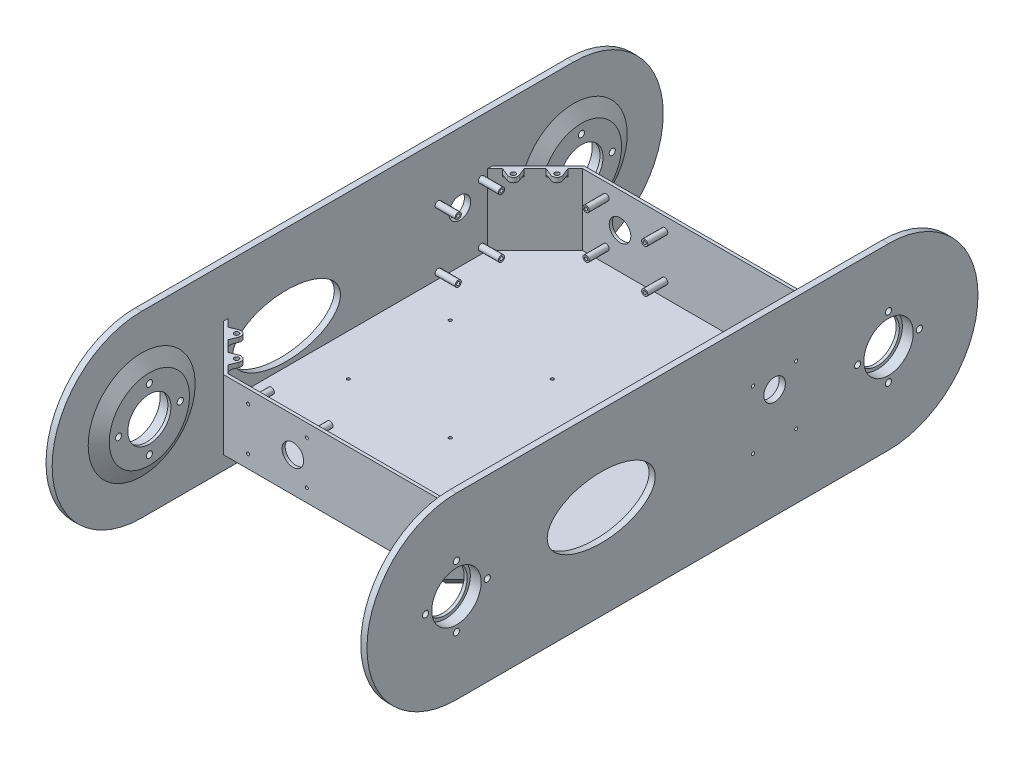
SolidWorks part; units mm, degrees
material "Zoltek Panex 33"
ref_plane "Front Plane" through (0, 0, 0) normal (0, 0, 1) x (1, 0, 0)
ref_plane "Top Plane" through (0, 0, 0) normal (0, 1, 0) x (1, 0, 0)
ref_plane "Right Plane" through (0, 0, 0) normal (1, 0, 0) x (0, 0, -1)
sketch "Sketch1" plane through (0, 0, 0) normal (0, 1, 0) x (1, 0, 0)
  line L1 (-100, -117) -> (100, -117)
  line L2 (-100, -117) -> (-100, 117)
  line L3 (-100, 117) -> (100, 117)
  line L4 (100, -117) -> (100, 117)
  line L5 (-100, -117) -> (100, 117) construction
  line L6 (-100, 117) -> (100, -117) construction
  point P0 (0, 0)
  dimension "D1" = 200
  dimension "D2" = 234
extrude "Boss-Extrude1" add sketch "Sketch1" along normal blind 52 contours L3 L4 L1 L2
chamfer "Chamfer1" distance 30 angle 45 4 edges at (-100, 26, -117) (100, 26, -117) (-100, 26, 117) (100, 26, 117)
sketch "Sketch2" plane through (100, 0, 0) normal (1, 0, 0) x (0, 0, -1)
  line L0 (117, 26) -> (-117, 26) construction
  line L1 (117, 52) -> (117, 0) construction
  line L2 (-117, 52) -> (-117, 0) construction
  line L3 (-140, 26) -> (140, 26) construction
  line L4 (-140, 84) -> (140, 84)
  line L5 (-140, -32) -> (140, -32)
  arc A0 (-140, 84) -> (-140, -32) centre (-140, 26) ccw
  arc A1 (140, -32) -> (140, 84) centre (140, 26) ccw
  point P8 (0, 26)
  dimension "D2" = 58
  dimension "D1" = 280
extrude "Boss-Extrude2" add sketch "Sketch2" along normal blind 4
ref_plane "Plane1" through (95, 0, 0) normal (-1, 0, 0) x (0, 0, 1)
sketch "Sketch3" plane through (95, 0, 0) normal (-1, 0, 0) x (0, 0, 1)
  circle A0 centre (140, 26) radius 16
  circle A1 centre (140, 26) radius 26
  dimension "D1" = 32
  dimension "D2" = 52
extrude "Boss-Extrude3" add sketch "Sketch3" against normal up to surface (5 mm away) draft 60 contours A1 up to face at (100, 26, 0) draft outward yes
sketch "Sketch4" plane through (95, 0, 0) normal (-1, 0, 0) x (0, 0, 1)
  circle A0 centre (140, 26) radius 14
  dimension "D1" = 28
extrude "Cut-Extrude1" cut sketch "Sketch4" against normal blind 2
sketch "Sketch5" plane through (97, 0, 0) normal (-1, 0, 0) x (0, 0, 1)
  circle A0 centre (140, 26) radius 16
  dimension "D1" = 32
extrude "Cut-Extrude2" cut sketch "Sketch5" against normal through all
mirror "Mirror1" about plane through (0, 0, 0) normal (0, 0, 1) of "Cut-Extrude2", "Cut-Extrude1", "Boss-Extrude3"
mirror "Mirror2" about plane through (0, 0, 0) normal (1, 0, 0) of "Mirror1", "Cut-Extrude2", "Cut-Extrude1", "Boss-Extrude3", "Boss-Extrude2"
sketch "Sketch6" plane through (-95, 0, 0) normal (1, 0, 0) x (0, 0, -1)
  line L0 (-140, 26) -> (-140, 46) construction
  circle A0 centre (-140, 26) radius 16 construction
  circle A1 centre (-140, 26) radius 16 construction
  circle A2 centre (-140, 46) radius 2
  circle A3 centre (-120, 26) radius 2
  circle A4 centre (-140, 6) radius 2
  circle A5 centre (-160, 26) radius 2
  point P13 (-140, 26)
  dimension "D1" = 4
  dimension "D2" = 20
  dimension "D3" = 4
extrude "Cut-Extrude3" cut sketch "Sketch6" against normal through all and the other way through all
mirror "Mirror3" about plane through (0, 0, 0) normal (0, 0, 1) of "Cut-Extrude3"
sketch "Sketch7" plane through (0, 52, 0) normal (0, 1, 0) x (1, 0, 0)
  line L0 (-100, 84.1716) -> (-69.1716, 115)
  line L1 (-100, 140) -> (-100, -140) construction
  line L2 (-69.1716, 115) -> (69.1716, 115)
  line L3 (0, 115) -> (0, 0) construction
  line L4 (0, 0) -> (-100, 0) construction
  line L5 (-70, 117) -> (-100, 87) construction
  line L6 (-70, 117) -> (70, 117) construction
  line L7 (-100, -84.1716) -> (-69.1716, -115)
  line L8 (-69.1716, -115) -> (69.1716, -115)
  line L9 (100, -84.1716) -> (69.1716, -115)
  line L10 (100, 84.1716) -> (69.1716, 115)
  line L11 (-100, -87) -> (-100, 87) construction
  line L12 (-100, -84.1716) -> (-100, 84.1716)
  line L13 (100, 140) -> (100, -140) construction
  line L14 (100, 84.1716) -> (100, -84.1716)
  point P16 (0, -115)
  dimension "D1" = 2
  dimension "D2" = 2
extrude "Cut-Extrude4" cut sketch "Sketch7" against normal blind 46 contours L0 L2 L10 L14 L9 L8 L7 L12
sketch "Sketch8" plane through (104, 0, 0) normal (1, 0, 0) x (0, 0, -1)
  line L0 (0, -32) -> (0, 84) construction
  line L1 (-140, -32) -> (140, -32) construction
  line L2 (140, 84) -> (-140, 84) construction
  line L3 (84.1716, 6) -> (84.1716, 52) construction
  line L4 (-84.1716, 6) -> (-84.1716, 52) construction
  line L5 (84.1716, 6) -> (84.1716, 52) construction
  line L6 (-84.1716, 6) -> (-84.1716, 52) construction
  line L7 (84.1716, 29) -> (-84.1716, 29) construction
  line L9 (80.1716, 10) -> (52.1716, 10) construction
  line L10 (80.1716, 10) -> (80.1716, 48) construction
  line L11 (80.1716, 48) -> (52.1716, 48) construction
  line L12 (52.1716, 10) -> (52.1716, 48) construction
  line L13 (80.1716, 10) -> (52.1716, 48) construction
  line L14 (80.1716, 48) -> (52.1716, 10) construction
  circle A0 centre (52.1716, 48) radius 1
  circle A1 centre (80.1716, 48) radius 1
  circle A2 centre (80.1716, 10) radius 1
  circle A3 centre (52.1716, 10) radius 1
  circle A4 centre (66.1716, 39) radius 7
  ellipse E0 centre (-46.1716, 29) end of major axis (-81.1716, 29) minor radius 20
  point P25 (66.1716, 48)
  point P37 (66.1716, 29)
  dimension "D7" = 2
  dimension "D8" = 14
  dimension "D1" = 20
  dimension "D2" = 35
  dimension "D3" = 3
  dimension "D4" = 38
  dimension "D5" = 28
  dimension "D6" = 4
  dimension "D9" = 9
extrude "Cut-Extrude5" cut sketch "Sketch8" against normal through all
chamfer "Chamfer3" distance 7 angle 45 6 edges at (-85, 0, -102) (85, 0, -102) (0, 0, -117) (85, 0, 102) (-85, 0, 102) (0, 0, 117)
sketch "Sketch9" plane through (0, 6, 0) normal (0, 1, 0) x (1, 0, 0)
  line L1 (-73, -33) -> (-7, -33) construction
  line L2 (-73, -33) -> (-73, 33) construction
  line L3 (-73, 33) -> (-7, 33) construction
  line L4 (-7, -33) -> (-7, 33) construction
  line L5 (-73, -33) -> (-7, 33) construction
  line L6 (-73, 33) -> (-7, -33) construction
  circle A0 centre (-73, 33) radius 1
  circle A1 centre (-7, 33) radius 1
  circle A2 centre (-7, -33) radius 1
  circle A3 centre (-73, -33) radius 1
  point P0 (-40, 0)
  point P10 (0, 0)
  point P11 (-38.851, 0)
  dimension "D3" = 2
  dimension "D4" = 40
  dimension "D1" = 66
  dimension "D2" = 66
extrude "Cut-Extrude6" cut sketch "Sketch9" against normal through all
sketch "Sketch10" plane through (0, 0, -117) normal (0, 0, -1) x (-1, 0, 0)
  line L0 (70, 29.5) -> (35, 29.5) construction
  line L1 (16, 15.5) -> (54, 15.5) construction
  line L2 (16, 15.5) -> (16, 43.5) construction
  line L3 (16, 43.5) -> (54, 43.5) construction
  line L4 (54, 15.5) -> (54, 43.5) construction
  line L5 (16, 15.5) -> (54, 43.5) construction
  line L6 (16, 43.5) -> (54, 15.5) construction
  line L7 (70, 7) -> (70, 52) construction
  circle A0 centre (16, 43.5) radius 1
  circle A1 centre (54, 43.5) radius 1
  circle A2 centre (54, 15.5) radius 1
  circle A3 centre (16, 15.5) radius 1
  point P0 (35, 29.5)
  point P14 (0, 0)
  point P15 (34.3735, 29.5)
  dimension "D3" = 2
  dimension "D4" = 35
  dimension "D1" = 38
  dimension "D2" = 28
extrude "Cut-Extrude7" cut sketch "Sketch10" against normal through all
sketch "Sketch11" plane through (100, 0, 0) normal (-1, 0, 0) x (0, 0, 1)
  circle A0 centre (-80.1716, 48) radius 2
  circle A1 centre (-52.1716, 48) radius 2
  circle A2 centre (-52.1716, 10) radius 2
  circle A3 centre (-80.1716, 10) radius 2
  circle A4 centre (-80.1716, 10) radius 1 construction
  circle A5 centre (-52.1716, 10) radius 1 construction
  circle A6 centre (-52.1716, 48) radius 1 construction
  circle A7 centre (-80.1716, 48) radius 1 construction
  circle A8 centre (-80.1716, 10) radius 1
  circle A9 centre (-52.1716, 10) radius 1
  circle A10 centre (-52.1716, 48) radius 1
  circle A11 centre (-80.1716, 48) radius 1
  dimension "D1" = 4
extrude "Boss-Extrude4" add sketch "Sketch11" along normal blind 13
mirror "Mirror4" about plane through (0, 0, 0) normal (1, 0, 0) of "Boss-Extrude4"
sketch "Sketch12" plane through (0, 0, -115) normal (0, 0, 1) x (1, 0, 0)
  circle A0 centre (-54, 43.5) radius 2
  circle A1 centre (-16, 43.5) radius 2
  circle A2 centre (-16, 15.5) radius 2
  circle A3 centre (-54, 15.5) radius 2
  circle A4 centre (-54, 15.5) radius 1 construction
  circle A5 centre (-16, 15.5) radius 1 construction
  circle A6 centre (-16, 43.5) radius 1 construction
  circle A7 centre (-54, 43.5) radius 1 construction
  circle A8 centre (-54, 15.5) radius 1
  circle A9 centre (-16, 15.5) radius 1
  circle A10 centre (-16, 43.5) radius 1
  circle A11 centre (-54, 43.5) radius 1
  point P2 (0, 0)
  point P5 (0, 0)
  point P8 (0, 0)
  point P11 (0, 0)
  dimension "D1" = 4
extrude "Boss-Extrude5" add sketch "Sketch12" along normal blind 13
mirror "Mirror5" about plane through (0, 0, 0) normal (0, 0, 1) of "Boss-Extrude5"
sketch "Sketch13" plane through (0, 0, 117) normal (0, 0, 1) x (1, 0, 0)
  line L0 (-16, 43.5) -> (-16, 15.5) construction
  line L1 (-16, 29.5) -> (-25, 29.5) construction
  circle A0 centre (-25, 29.5) radius 7
  dimension "D1" = 14
  dimension "D2" = 9
extrude "Cut-Extrude8" cut sketch "Sketch13" against normal blind 3
sketch "Sketch14" plane through (0, 0, -117) normal (0, 0, -1) x (-1, 0, 0)
  line L0 (54, 43.5) -> (54, 15.5) construction
  line L1 (54, 29.5) -> (45, 29.5) construction
  circle A0 centre (45, 29.5) radius 7
  dimension "D1" = 14
  dimension "D2" = 9
extrude "Cut-Extrude9" cut sketch "Sketch14" against normal blind 3
sketch "Sketch15" plane through (0, 52, 0) normal (0, 1, 0) x (1, 0, 0)
  line L0 (-100, 78.5147) -> (-63.5147, 115) construction
  line L1 (-100, -84.1716) -> (-100, 84.1716) construction
  line L2 (-69.1716, 115) -> (69.1716, 115) construction
  line L3 (-100, 84.1716) -> (-69.1716, 115) construction
  line L4 (-81.7574, 96.7574) -> (-47.3087, 62.3087) construction
  line L5 (-100, 84.1716) -> (-69.1716, 115) construction
  line L6 (-95.1924, 88.9792) -> (-89.9327, 86.8969)
  line L7 (-88.8284, 89.6863) -> (-91.6569, 92.5147) construction
  line L8 (-88.1213, 96.0503) -> (-86.0391, 90.7906)
  line L9 (-73.9792, 110.1924) -> (-71.8969, 104.9327)
  line L10 (-81.0503, 103.1213) -> (-75.7906, 101.0391)
  line L11 (-95.1924, 88.9792) -> (-88.1213, 96.0503)
  line L12 (-81.0503, 103.1213) -> (-73.9792, 110.1924)
  line L13 (0, 0) -> (0, 117.5947) construction
  line L14 (-89.6858, 0) -> (89.6858, 0) construction
  line L15 (81.0503, 103.1213) -> (73.9792, 110.1924)
  line L16 (73.9792, 110.1924) -> (71.8969, 104.9327)
  line L17 (81.0503, 103.1213) -> (75.7906, 101.0391)
  line L18 (95.1924, 88.9792) -> (89.9327, 86.8969)
  line L19 (88.1213, 96.0503) -> (86.0391, 90.7906)
  line L20 (95.1924, 88.9792) -> (88.1213, 96.0503)
  line L21 (95.1924, -88.9792) -> (88.1213, -96.0503)
  line L22 (88.1213, -96.0503) -> (86.0391, -90.7906)
  line L23 (95.1924, -88.9792) -> (89.9327, -86.8969)
  line L24 (81.0503, -103.1213) -> (75.7906, -101.0391)
  line L25 (73.9792, -110.1924) -> (71.8969, -104.9327)
  line L26 (81.0503, -103.1213) -> (73.9792, -110.1924)
  line L27 (-81.0503, -103.1213) -> (-73.9792, -110.1924)
  line L28 (-73.9792, -110.1924) -> (-71.8969, -104.9327)
  line L29 (-81.0503, -103.1213) -> (-75.7906, -101.0391)
  line L30 (-95.1924, -88.9792) -> (-89.9327, -86.8969)
  line L31 (-88.1213, -96.0503) -> (-86.0391, -90.7906)
  line L32 (-95.1924, -88.9792) -> (-88.1213, -96.0503)
  circle A0 centre (-88.8284, 89.6863) radius 1.5
  circle A1 centre (-74.6863, 103.8284) radius 1.5
  arc A2 (-89.9327, 86.8969) -> (-86.0391, 90.7906) centre (-88.8284, 89.6863) ccw
  arc A3 (-71.8969, 104.9327) -> (-75.7906, 101.0391) centre (-74.6863, 103.8284) cw
  circle A4 centre (74.6863, 103.8284) radius 1.5
  arc A5 (71.8969, 104.9327) -> (75.7906, 101.0391) centre (74.6863, 103.8284) ccw
  circle A6 centre (88.8284, 89.6863) radius 1.5
  arc A7 (89.9327, 86.8969) -> (86.0391, 90.7906) centre (88.8284, 89.6863) cw
  circle A8 centre (88.8284, -89.6863) radius 1.5
  arc A9 (89.9327, -86.8969) -> (86.0391, -90.7906) centre (88.8284, -89.6863) ccw
  circle A10 centre (74.6863, -103.8284) radius 1.5
  arc A11 (71.8969, -104.9327) -> (75.7906, -101.0391) centre (74.6863, -103.8284) cw
  circle A12 centre (-74.6863, -103.8284) radius 1.5
  arc A13 (-71.8969, -104.9327) -> (-75.7906, -101.0391) centre (-74.6863, -103.8284) ccw
  circle A14 centre (-88.8284, -89.6863) radius 1.5
  arc A15 (-89.9327, -86.8969) -> (-86.0391, -90.7906) centre (-88.8284, -89.6863) cw
  dimension "D1" = 4
  dimension "D2" = 3
  dimension "D3" = 6
  dimension "D4" = 10
  dimension "D5" = 10
extrude "Boss-Extrude6" add sketch "Sketch15" against normal blind 3
fillet "Fillet1" radius 2 8 edges at (-91.6569, 49, 92.5147) (-77.5147, 49, 106.6569) (91.6569, 49, 92.5147) (77.5147, 49, 106.6569) (91.6569, 49, -92.5147) (77.5147, 49, -106.6569) (-91.6569, 49, -92.5147) (-77.5147, 49, -106.6569)
